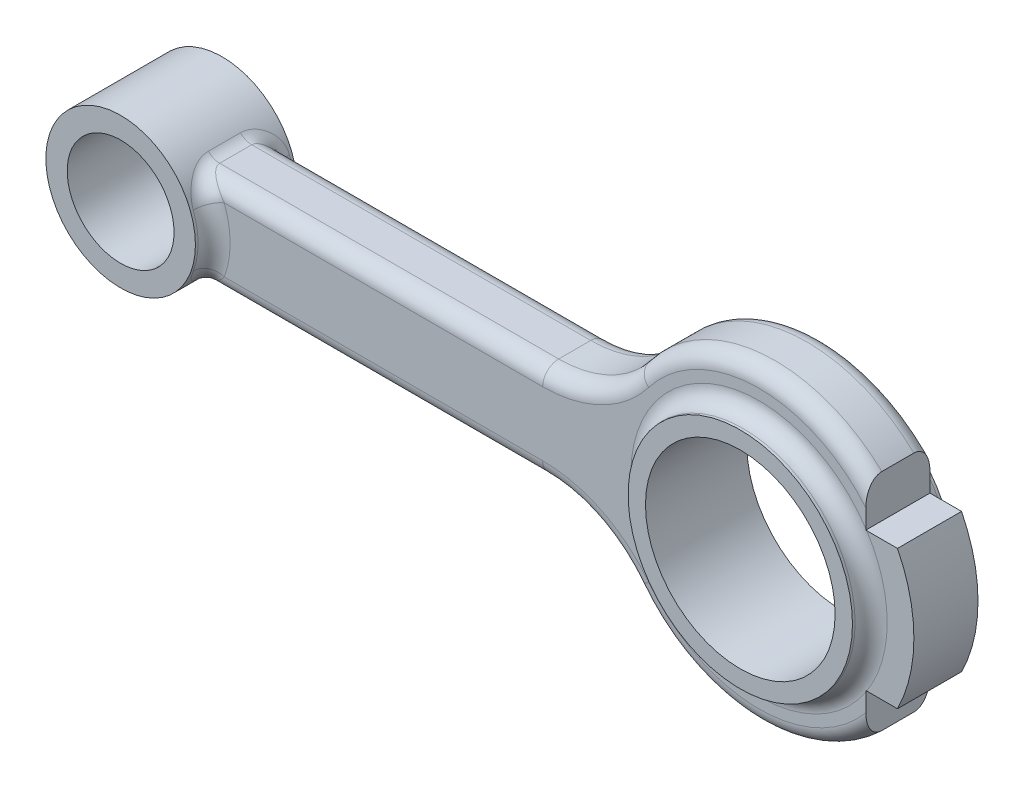
SolidWorks part; units mm, degrees
material "AISI 304"
ref_plane "Front Plane" through (0, 0, 0) normal (0, 0, 1) x (1, 0, 0)
ref_plane "Top Plane" through (0, 0, 0) normal (0, 1, 0) x (1, 0, 0)
ref_plane "Right Plane" through (0, 0, 0) normal (1, 0, 0) x (0, 0, -1)
sketch "Sketch1" plane through (0, 0, 0) normal (0, 0, 1) x (1, 0, 0)
  circle A0 centre (0, 0) radius 10
  circle A1 centre (0, 0) radius 14
  dimension "D1" = 20
  dimension "D2" = 28
extrude "Boss-Extrude1" add sketch "Sketch1" along normal mid plane 19
ref_plane "Plane1" through (14, 0, 0) normal (1, 0, 0) x (0, 0, -1)
sketch "Sketch2" plane through (0, 0, 0) normal (0, 0, 1) x (1, 0, 0)
  line L0 (0, 0) -> (116, 0) construction
  circle A0 centre (116, 0) radius 17.75
  circle A1 centre (116, 0) radius 29
  dimension "D1" = 35.5
  dimension "D2" = 58
  dimension "D3" = 116
extrude "Boss-Extrude2" add sketch "Sketch2" along normal mid plane 12 separate body
sketch "Sketch3" plane through (0, 0, 6) normal (0, 0, 1) x (1, 0, 0)
  circle A0 centre (116, 0) radius 21
  circle A1 centre (116, 0) radius 17.75
  dimension "D1" = 42
  dimension "D2" = 35.5
extrude "Boss-Extrude3" add sketch "Sketch3" along normal blind 3.5
sketch "Sketch4" plane through (0, 0, -6) normal (0, 0, -1) x (-1, 0, 0)
  circle A0 centre (-116, 0) radius 21
  circle A1 centre (-116, 0) radius 17.75
  dimension "D1" = 42
  dimension "D2" = 35.5
extrude "Boss-Extrude4" add sketch "Sketch4" along normal blind 3.5
fillet "Fillet1" radius 3 1 edges at (137, 0, 6)
fillet "Fillet2" radius 3 1 edges at (137, 0, -6)
sketch "Sketch5" plane through (0, 0, 9.5) normal (0, 0, 1) x (1, 0, 0)
  line L0 (116, 29) -> (136, 29) construction
  line L1 (136, 29) -> (136, 13)
  line L2 (136, 13) -> (161, 13)
  line L3 (161, 13) -> (161, 29)
  line L4 (161, 29) -> (136, 29)
  line L5 (116, 0) -> (161, 0) construction
  line L6 (161, -13) -> (161, -29)
  line L7 (136, -13) -> (161, -13)
  line L8 (136, -29) -> (136, -13)
  line L9 (161, -29) -> (136, -29)
  circle A0 centre (116, 0) radius 29 construction
  dimension "D1" = 20
  dimension "D2" = 116
  dimension "D3" = 16
  dimension "D4" = 25
extrude "Cut-Extrude1" cut sketch "Sketch5" against normal through all
sketch "Sketch6" plane through (0, 0, 0) normal (0, 0, 1) x (1, 0, 0)
  line L0 (0, 0) -> (14, 0) construction
  line L3 (14, -9) -> (88.4319, -9)
  line L4 (88.4319, -9) -> (88.4319, 9)
  line L5 (88.4319, 9) -> (14, 9)
  line L6 (14, 9) -> (10, 9)
  line L7 (10, 9) -> (10, 0)
  line L8 (10, 0) -> (10, -9)
  line L9 (10, -9) -> (14, -9)
  line L10 (14, 0) -> (14, 9) construction
  line L11 (14, 0) -> (14, -9) construction
  circle A0 centre (0, 0) radius 14 construction
  arc A1 (136, 21) -> (136, -21) centre (116, 0) ccw construction
  circle A2 centre (0, 0) radius 10 construction
  dimension "D1" = 18
extrude "Boss-Extrude5" add sketch "Sketch6" along normal mid plane 12
fillet "Fillet3" radius 22 1 edges at (88.4319, 9, 0)
fillet "Fillet4" radius 22 1 edges at (88.4319, -9, 0)
fillet "Fillet5" radius 3 12 edges at (43.1134, -9, -6) (43.1134, -9, 6) (113.7339, 28.9113, 6) (113.7339, 28.9113, -6) (43.1134, 9, -6) (43.1134, 9, 6) (85.2449, 11.2744, -6) (85.2449, 11.2744, 6) (113.7339, -28.9113, 6) (113.7339, -28.9113, -6) (85.2449, -11.2744, -6) (85.2449, -11.2744, 6)
fillet "Fillet6" radius 3 8 edges at (11.0859, 8.55, -4.5804) (11.4597, -8.042, -5.1978) (11.0859, -8.55, 4.5804) (11.4597, 8.042, 5.1978) (14, 0, -6) (10.7238, 9, 0) (14, 0, 6) (10.7238, -9, 0)
